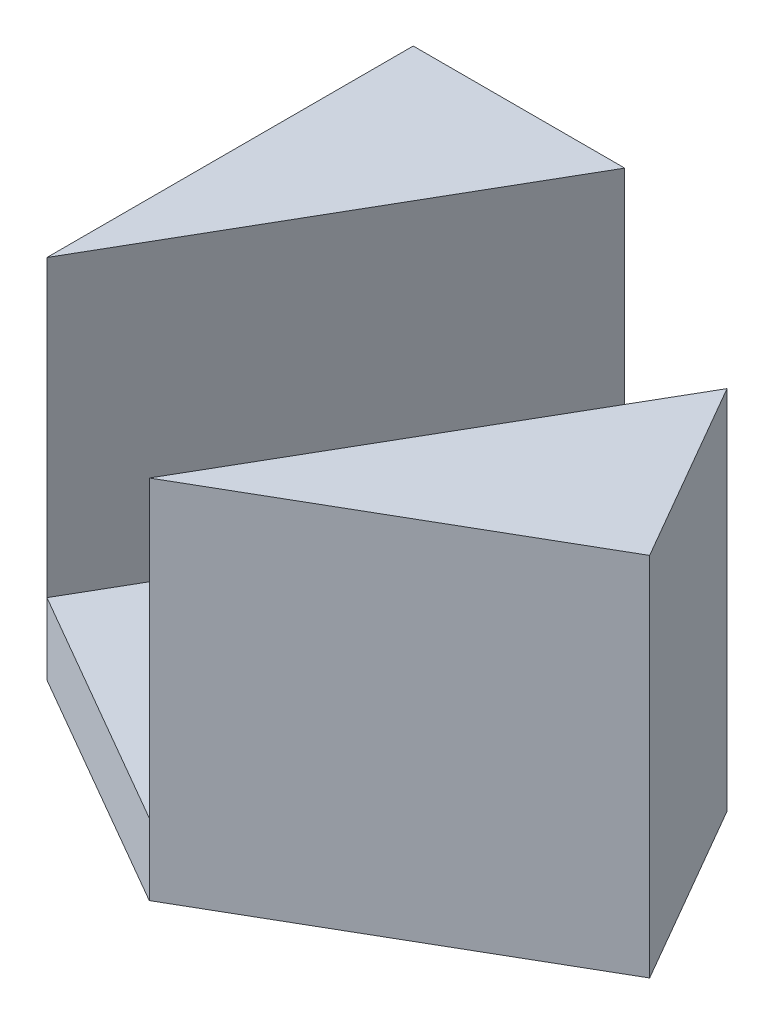
SolidWorks part; units mm, degrees
ref_plane "Front Plane" through (0, 0, 0) normal (0, 0, 1) x (1, 0, 0)
ref_plane "Top Plane" through (0, 0, 0) normal (0, 1, 0) x (1, 0, 0)
ref_plane "Right Plane" through (0, 0, 0) normal (1, 0, 0) x (0, 0, -1)
sketch "Sketch1" plane through (0, 0, 0) normal (0, 1, 0) x (1, 0, 0)
  line L186 (-109.6495, 21.2673) -> (-99.4737, 15.3923)
  line L188 (-118.5363, 5.875) -> (-109.6495, 21.2673)
  line L189 (-118.5363, 5.875) -> (-108.3605, 0)
  line L193 (-108.3605, 0) -> (-95.0303, 7.6962)
  line L194 (-95.0303, 7.6962) -> (-99.4737, 15.3923)
  line L195 (-108.3605, 0) -> (-99.4737, 15.3923)
  line L211 (-118.5363, 21.2673) -> (-109.6495, 21.2673)
  line L221 (-118.5363, 21.2673) -> (-118.5363, 5.875)
extrude "Boss-Extrude3" add sketch "Sketch1" along normal blind 15.38 contours L195 L193 L194 | L211 L221 L188
extrude "Boss-Extrude7" add sketch "Sketch1<8>" along normal blind 3 contours L221 | L189 L195 L186 L188 | L193 region at (-109.005, 0, -10.6337)
sketch "Sketch1<8>" plane through (0, 0, 0) normal (0, 1, 0) x (1, 0, 0) same geometry as "Sketch1"
